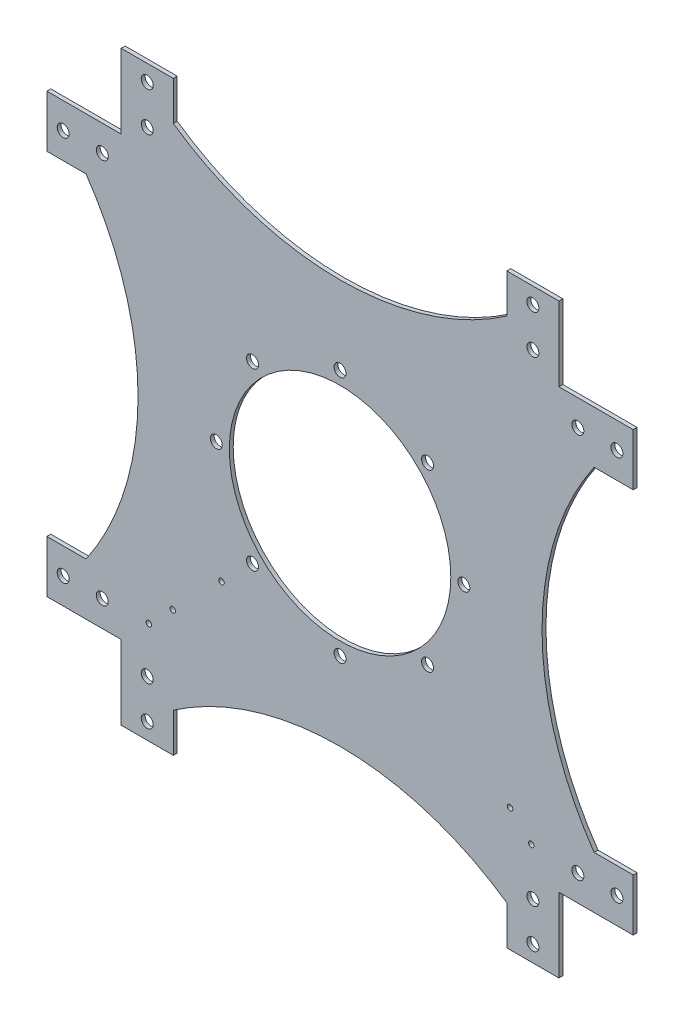
SolidWorks part; units mm, degrees
ref_plane "Front Plane" through (0, 0, 0) normal (0, 0, 1) x (1, 0, 0)
ref_plane "Top Plane" through (0, 0, 0) normal (0, 1, 0) x (1, 0, 0)
ref_plane "Right Plane" through (0, 0, 0) normal (1, 0, 0) x (0, 0, -1)
sketch "Sketch1" plane through (0, 0, 0) normal (0, 0, 1) x (1, 0, 0)
  line L0 (0, 0) -> (367.2182, 0) construction
  line L1 (0, 0) -> (0, -316.5866) construction
  line L2 (0, 0) -> (168, 168) construction
  line L3 (0, 0) -> (168, -168) construction
  line L4 (168, 168) -> (168, 225)
  line L5 (168, 168) -> (225, 168)
  line L6 (168, 225) -> (128, 225)
  line L7 (128, 225) -> (128, 195)
  line L8 (0, 0) -> (-168, 168) construction
  line L9 (0, 0) -> (-168, -168) construction
  line L10 (0, 0) -> (-199.7109, 0) construction
  line L11 (-168, 168) -> (-168, 225)
  line L12 (-168, 225) -> (-128, 225)
  line L13 (-128, 225) -> (-128, 195)
  line L14 (168, -168) -> (225, -168)
  line L15 (225, -168) -> (225, -128)
  line L16 (225, -128) -> (195, -128)
  line L17 (225, 168) -> (225, 128)
  line L18 (225, 128) -> (195, 128)
  line L19 (168, -168) -> (168, -225)
  line L20 (168, -225) -> (128, -225)
  line L21 (128, -225) -> (128, -195)
  line L22 (-128, -225) -> (-128, -195)
  line L23 (-168, -225) -> (-128, -225)
  line L24 (-168, -168) -> (-168, -225)
  line L25 (-168, -168) -> (-225, -168)
  line L26 (-225, -168) -> (-225, -128)
  line L27 (-225, -128) -> (-195, -128)
  line L28 (-225, 128) -> (-195, 128)
  line L29 (-225, 168) -> (-225, 128)
  line L30 (-168, 168) -> (-225, 168)
  circle A0 centre (0, 0) radius 85
  arc A1 (-128, 195) -> (128, 195) centre (0, 380.0432) ccw
  arc A2 (195, 128) -> (195, -128) centre (380.0432, 0) ccw
  arc A3 (-128, -195) -> (128, -195) centre (0, -380.0432) cw
  arc A4 (-195, 128) -> (-195, -128) centre (-380.0432, 0) cw
  dimension "D4" = 170
  dimension "D9" = 225
  dimension "D1" = 45
  dimension "D3" = 57
  dimension "D5" = 40
  dimension "D6" = 45
  dimension "D7" = 45
  dimension "D8" = 30
  dimension "D10" = 225
sheet metal parameters "Sheet-Metal1" thickness 3 parameters "D1"=1
base flange "Base-Flange1" sketch "Sketch1" thickness 3 reverse thickness direction yes parameters "D1"=1
sketch "Sketch2" plane through (0, 0, 3) normal (0, 0, 1) x (1, 0, 0)
  line L0 (168, 168) -> (168, 225) construction
  line L1 (168, 225) -> (128, 225) construction
  line L2 (225, 128) -> (225, 168) construction
  line L3 (225, 168) -> (168, 168) construction
  line L4 (0, 0) -> (260.8486, 0) construction
  line L5 (0, 0) -> (0, -250.4708) construction
  circle A0 centre (148, 212.5) radius 4.6
  circle A1 centre (148, 182.5) radius 4.6
  circle A2 centre (182.5, 148) radius 4.6
  circle A3 centre (212.5, 148) radius 4.6
  circle A4 centre (212.5, -148) radius 4.6
  circle A5 centre (182.5, -148) radius 4.6
  circle A6 centre (148, -182.5) radius 4.6
  circle A7 centre (148, -212.5) radius 4.6
  circle A8 centre (-148, -212.5) radius 4.6
  circle A9 centre (-148, -182.5) radius 4.6
  circle A10 centre (-182.5, -148) radius 4.6
  circle A11 centre (-212.5, -148) radius 4.6
  circle A12 centre (-212.5, 148) radius 4.6
  circle A13 centre (-182.5, 148) radius 4.6
  circle A14 centre (-148, 182.5) radius 4.6
  circle A15 centre (-148, 212.5) radius 4.6
  point P8 (168, 196.5)
  dimension "D2" = 9.2
  dimension "D1" = 20
  dimension "D3" = 12.5
  dimension "D4" = 30
  dimension "D5" = 30
  dimension "D6" = 12.5
  dimension "D7" = 20
extrude "Extrude1" cut sketch "Sketch2" against normal blind 3 normal cut yes
sketch "Sketch3" plane through (0, 0, 3) normal (0, 0, 1) x (1, 0, 0)
  line L0 (0, 0) -> (220.4396, 0) construction
  line L1 (0, 0) -> (0, -219.5819) construction
  line L2 (0, 0) -> (178.1909, 178.1909) construction
  circle A0 centre (0, 0) radius 95 construction
  circle A1 centre (0, 95) radius 4.6
  circle A2 centre (-95, 0) radius 4.6 construction
  circle A3 centre (0, -95) radius 4.6 construction
  circle A4 centre (95, 0) radius 4.6 construction
  dimension "D2" = 9.2
  dimension "D3" = 190
  dimension "D1" = 45
extrude "Extrude2" cut sketch "Sketch3" against normal blind 3 normal cut yes
pattern_circular "CirPattern1" count 8 over 360 about axis through (0, 0, 3) along (0, 0, 1) of "Extrude2"
sketch "Sketch4" plane through (0, 0, 3) normal (0, 0, 1) x (1, 0, 0)
  line L0 (-168, -168) -> (0, 0) construction
  line L1 (0, 0) -> (168, -168) construction
  circle A0 centre (-146.7868, -146.7868) radius 2.1
  circle A1 centre (-128.402, -128.402) radius 2.1
  circle A2 centre (-90.9254, -90.9254) radius 2.1
  circle A3 centre (130.5233, -130.5233) radius 2.1
  circle A4 centre (146.7868, -146.7868) radius 2.1
  dimension "D1" = 30
  dimension "D3" = 53
  dimension "D4" = 4.2
  dimension "D5" = 23
  dimension "D6" = 30
  dimension "D2" = 26
extrude "Cut-Extrude1" cut sketch "Sketch4" against normal blind 3 normal cut yes
flat pattern "Flat-Pattern1" [suppressed]
sketch "Bend-Lines1" plane through (0, 0, 0) normal (0, 1, 0) x (-1, 0, 0)
